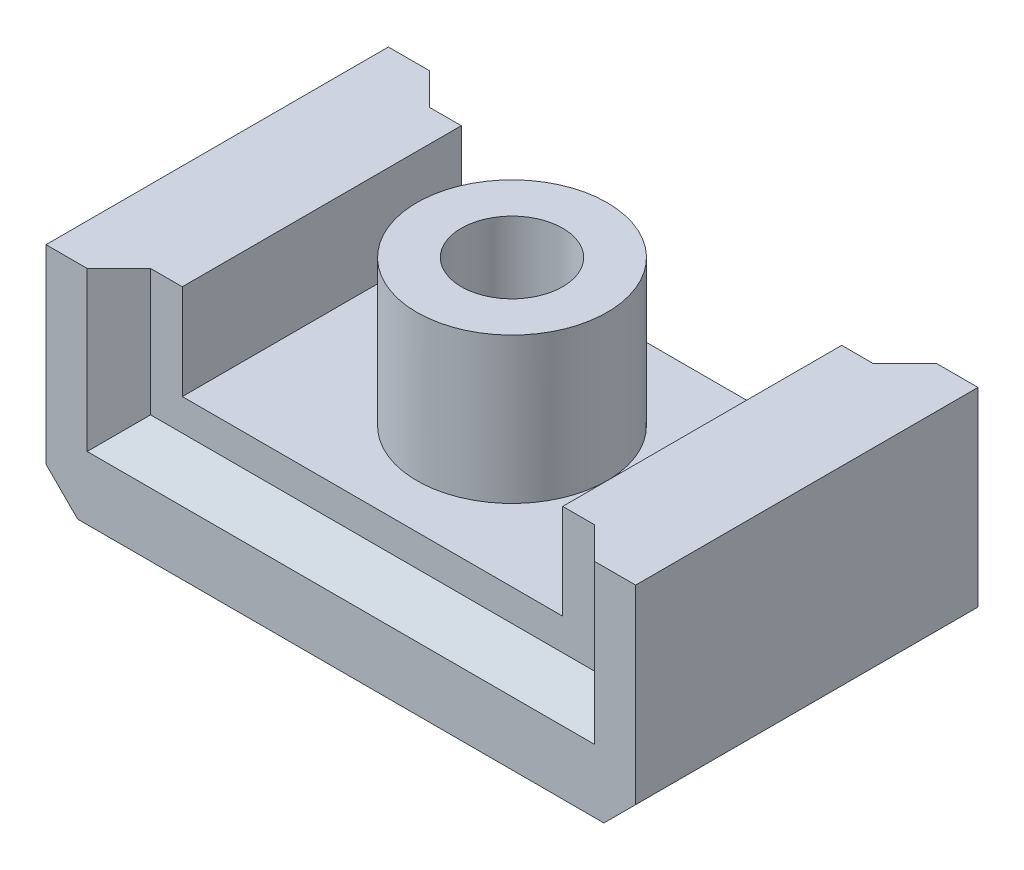
SolidWorks part; units mm, degrees
ref_plane "Front" through (0, 0, 0) normal (0, 0, 1) x (1, 0, 0)
ref_plane "Top" through (0, 0, 0) normal (0, 1, 0) x (1, 0, 0)
ref_plane "Right" through (0, 0, 0) normal (1, 0, 0) x (0, 0, -1)
sketch "Sketch1" plane through (0, 0, 0) normal (0, 0, 1) x (1, 0, 0)
  line L0 (0, 0) -> (18.6, 0)
  line L1 (18.6, 0) -> (18.6, 7)
  line L2 (18.6, 7) -> (15.3, 7)
  line L3 (15.3, 7) -> (15.3, 4)
  line L4 (15.3, 4) -> (3.3, 4)
  line L5 (3.3, 4) -> (3.3, 7)
  line L6 (3.3, 7) -> (0, 7)
  line L7 (0, 7) -> (0, 0)
  dimension "D1" = 12
  dimension "D2" = 18.6
  dimension "D3" = 4
  dimension "D4" = 7
extrude "Boss-Extrude1" add sketch "Sketch1" along normal blind 10.8
sketch "Sketch2" plane through (0, 4, 0) normal (0, 1, 0) x (1, 0, 0)
  line L0 (9.3, 0) -> (9.3, -10.8) construction
  line L1 (15.3, 0) -> (3.3, 0) construction
  line L2 (15.3, -10.8) -> (3.3, -10.8) construction
  circle A0 centre (9.3, -5.4) radius 3
  dimension "D1" = 6
extrude "Boss-Extrude2" add sketch "Sketch2" along normal blind 4.6
sketch "Sketch3" plane through (0, 8.6, 0) normal (0, 1, 0) x (1, 0, 0)
  circle A0 centre (9.3, -5.4) radius 1.6
  dimension "D1" = 3.2
extrude "Cut-Extrude1" cut sketch "Sketch3" against normal through all
chamfer "Chamfer1" distance 1 angle 45 2 edges at (0, 0, 5.4) (18.6, 0, 5.4)
sketch "Sketch4" plane through (0, 0, 0) normal (0, 0, -1) x (-1, 0, 0)
  line L0 (-18.6, 7) -> (-15.3, 7) construction
  line L1 (-17.3, 7) -> (-1.3, 7)
  line L2 (-17.3, 7) -> (-17.3, 2)
  line L3 (-17.3, 2) -> (-1.3, 2)
  line L4 (-1.3, 7) -> (-1.3, 2)
  line L7 (-15.3, 4) -> (-3.3, 4) construction
  line L8 (-15.3, 7) -> (-15.3, 4) construction
  line L9 (-3.3, 4) -> (-3.3, 7) construction
  dimension "D1" = 2
  dimension "D2" = 2
  dimension "D3" = 2
extrude "Cut-Extrude2" cut sketch "Sketch4" against normal blind 1
chamfer "Chamfer2" distance 1 angle 45 3 edges at (1.3, 4.5, 1) (17.3, 4.5, 1) (9.3, 2, 1)
ref_plane "Plane1" through (0, 0, 5.4) normal (0, 0, -1) x (-1, 0, 0)
mirror "Mirror1" about plane through (0, 0, 5.4) normal (0, 0, -1) of "Chamfer2", "Cut-Extrude2"
